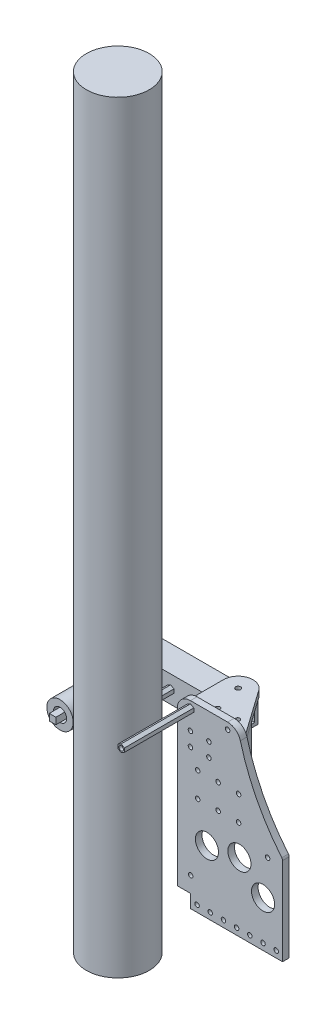
SolidWorks part; units mm, degrees
ref_plane "Front Plane" through (0, 0, 0) normal (0, 0, 1) x (1, 0, 0)
ref_plane "Top Plane" through (0, 0, 0) normal (0, 1, 0) x (1, 0, 0)
ref_plane "Right Plane" through (0, 0, 0) normal (1, 0, 0) x (0, 0, -1)
sketch "Elevation Bar" plane through (0, 0, 0) normal (0, 1, 0) x (1, 0, 0)
  circle A0 centre (0, 0) radius 30.226
  dimension "D1" = 60.452
extrude "Elevation Bar Part" add sketch "Elevation Bar" along normal blind 734.06
sketch "Pole and Drivetrain Pos" plane through (0, 0, 0) normal (0, 0, 1) x (1, 0, 0)
  line L0 (0, 0) -> (172.1794, 0) construction
  line L1 (-30.226, 0) -> (-30.226, 734.06) construction
  line L2 (-30.226, 734.06) -> (30.226, 734.06) construction
  line L3 (30.226, 734.06) -> (30.226, 0) construction
  line L4 (30.226, 0) -> (30.226, 734.06) construction
  line L5 (636.651, 41.275) -> (27.051, 41.275) construction
  line L6 (636.651, 53.975) -> (27.051, 53.975)
  line L7 (636.651, 53.975) -> (636.651, 28.575)
  line L8 (636.651, 28.575) -> (27.051, 28.575)
  line L9 (27.051, 53.975) -> (27.051, 28.575)
  line L10 (-30.226, 93.98) -> (30.226, 93.98) construction
  line L11 (33.2486, 0) -> (-33.2486, 0) construction
  line L12 (30.226, 185.42) -> (-30.226, 185.42) construction
  line L13 (30.226, 276.86) -> (-30.226, 276.86) construction
  line L14 (30.226, 368.3) -> (-30.226, 368.3) construction
  line L15 (30.226, 459.74) -> (-30.226, 459.74) construction
  line L16 (30.226, 551.18) -> (-30.226, 551.18) construction
  line L17 (30.226, 642.62) -> (-30.226, 642.62) construction
  line L18 (30.226, 73.152) -> (750.8896, 73.152) construction
  circle A0 centre (579.501, 41.275) radius 41.275 construction
  circle A1 centre (84.201, 41.275) radius 41.275 construction
  circle A2 centre (331.851, 41.275) radius 41.275 construction
  circle A3 centre (84.201, 41.275) radius 25.4
  point P24 (331.851, 41.275)
  dimension "D2" = 82.55
  dimension "D5" = 50.8
  dimension "D1" = 609.6
  dimension "D3" = 25.4
  dimension "D6" = 93.98
  dimension "D7" = 185.42
  dimension "D8" = 276.86
  dimension "D9" = 368.3
  dimension "D10" = 459.74
  dimension "D11" = 551.18
  dimension "D12" = 642.62
  dimension "D13" = 73.152
  dimension "D14" = 57.15
  dimension "D4" = 57.15
  dimension "D15" = 6.35
sketch "Driving Wheels Geo" plane through (0, 0, 0) normal (0, 0, 1) x (1, 0, 0)
  line L0 (-30.226, 182.88) -> (-30.226, 101.727) construction
  line L1 (55.626, 101.727) -> (30.226, 101.727) construction
  line L2 (-30.226, 0) -> (-30.226, 734.06) construction
  line L3 (30.226, 734.06) -> (30.226, 0) construction
  line L5 (30.226, 101.727) -> (-30.226, 101.727) construction
  line L6 (-30.226, 182.88) -> (30.226, 101.727) construction
  line L7 (31.8135, 101.727) -> (-30.226, 182.88) construction
  line L8 (30.226, 227.417) -> (203.668, 53.975) construction
  line L9 (-42.926, 195.58) -> (44.8729, 195.58) construction
  line L10 (30.226, 73.152) -> (750.8896, 73.152) construction
  line L11 (636.651, 53.975) -> (27.051, 53.975) construction
  line L14 (-42.926, 170.18) -> (44.8729, 170.18) construction
  line L15 (44.8729, 170.18) -> (44.8729, 195.58) construction
  line L16 (81.026, 28.575) -> (81.026, 257.175) construction
  line L17 (32.1729, 195.58) -> (57.5729, 195.58) construction
  line L18 (32.1729, 195.58) -> (32.1729, 170.18) construction
  line L19 (32.1729, 170.18) -> (57.5729, 170.18) construction
  line L20 (57.5729, 195.58) -> (57.5729, 170.18) construction
  line L21 (32.1729, 195.58) -> (57.5729, 170.18) construction
  line L22 (32.1729, 170.18) -> (57.5729, 195.58) construction
  line L23 (636.651, 28.575) -> (27.051, 28.575) construction
  line L24 (284.226, 257.175) -> (81.026, 257.175) construction
  line L25 (284.226, 257.175) -> (284.226, 53.975) construction
  line L26 (81.026, 257.175) -> (30.226, 257.175) construction
  circle A1 centre (55.626, 101.727) radius 25.4
  circle A3 centre (-42.926, 182.88) radius 12.7
  circle A4 centre (81.026, 104.775) radius 50.8 construction
  circle A5 centre (55.626, 101.727) radius 23.8125 construction
  circle A7 centre (284.226, 257.175) radius 203.2 construction
  point P28 (44.8729, 182.88)
  dimension "D1" = 50.8
  dimension "D2" = 1.5875
  dimension "D3" = 52.603
  dimension "D4" = 3.175
  dimension "D5" = 182.88
  dimension "D8" = 101.6
  dimension "D6" = 25.4
  dimension "D13" = 3.175
  dimension "D14" = 50.8
  dimension "D16" = 406.4
  dimension "D7" = 81.153
  dimension "D9" = 45
  dimension "D10" = 53.317
  dimension "D11" = 25.4
  dimension "D12" = 47.752
ref_plane "Plane1" through (0, 182.88, 0) normal (0, 1, 0) x (1, 0, 0)
sketch "Clamp Geo" plane through (0, 182.88, 0) normal (0, 1, 0) x (1, 0, 0)
  line L0 (-42.926, -19.8438) -> (-42.926, 87.3125) construction
  line L3 (27.051, 228.6) -> (27.051, -228.6) construction
  line L4 (47.6, 61.9125) -> (-49.276, 61.9125)
  line L5 (47.6, 61.9125) -> (47.6, 87.3125)
  line L6 (47.6, 87.3125) -> (-49.276, 87.3125)
  line L7 (-49.276, 61.9125) -> (-49.276, 87.3125)
  line L10 (-46.101, 87.3125) -> (-39.751, 87.3125)
  line L11 (-46.101, 87.3125) -> (-46.101, -19.8438)
  line L12 (-46.101, -19.8438) -> (-39.751, -19.8438)
  line L13 (-39.751, 87.3125) -> (-39.751, -19.8438)
  line L14 (-55.626, 12.7) -> (-30.226, 12.7) construction
  line L15 (-55.626, 12.7) -> (-55.626, -12.7) construction
  line L16 (-55.626, -12.7) -> (-30.226, -12.7) construction
  line L17 (-30.226, 12.7) -> (-30.226, -12.7) construction
  line L18 (-55.626, 12.7) -> (-30.226, -12.7) construction
  line L19 (-55.626, -12.7) -> (-30.226, 12.7) construction
  line L20 (0, -30.226) -> (0, 30.226) construction
  line L21 (-30.226, 0) -> (30.226, 0) construction
  line L22 (-46.101, 80.9625) -> (-42.926, 80.9625) construction
  line L23 (-39.751, 74.6125) -> (-46.101, 74.6125)
  line L24 (-46.101, 74.6125) -> (-46.101, 87.3125) construction
  line L25 (-39.751, 61.9125) -> (-39.751, 87.3125) construction
  line L26 (47.6, 74.6125) -> (41.25, 74.6125) construction
  line L27 (-11.049, 36.5125) -> (-11.049, 61.9125) construction
  line L28 (-14.224, 61.9125) -> (-7.874, 61.9125)
  line L29 (-14.224, 61.9125) -> (-14.224, 36.5125)
  line L30 (-14.224, 36.5125) -> (-7.874, 36.5125)
  line L31 (-7.874, 61.9125) -> (-7.874, 36.5125)
  circle A0 centre (0, 0) radius 30.226 construction
  circle A3 centre (-42.926, 80.9625) radius 1.8288
  circle A5 centre (-42.926, 68.2625) radius 1.8288
  circle A6 centre (41.25, 74.6125) radius 3.175
  circle A7 centre (41.25, 74.6125) radius 14.199 construction
  point P14 (-42.926, 0)
  point P32 (-39.751, 74.6125)
  point P34 (-46.101, 74.6125)
  point P36 (-42.926, 74.6125)
  point P42 (47.6, 74.6125)
  dimension "D1" = 60.452
  dimension "D4" = 61.9125
  dimension "D7" = 3.6576
  dimension "D8" = 3.175
  dimension "D10" = 6.35
  dimension "D11" = 3.175
  dimension "D12" = 25.4
  dimension "D2" = 457.2
  dimension "D3" = 25.4
  dimension "D5" = 6.35
  dimension "D6" = 25.4
  dimension "D9" = 96.876
  dimension "D13" = 7.1437
  dimension "D14" = 6.35
  dimension "D15" = 38.1
extrude "Boss-Extrude1" add sketch "Clamp Geo" along normal blind 12.7 and the other way blind 12.7 separate body contours L6 L13 L4 L5 A6 | L11 L6 L7 L4 | L13 L23 L11 L4 A5 | L23 L13 L6 L11 A3 region at (3.384, 182.88, -74.6125) region at (-39.893, 182.88, -80.9625) region at (-42.926, 182.88, -62.0545) region at (-47.6885, 182.88, -74.6125)
sketch "Locked Setting Geo" plane through (0, 182.88, 0) normal (0, 1, 0) x (1, 0, 0)
  line L0 (30.9086, 201.0486) -> (105.8246, 124.4323) construction
  line L1 (27.7805, 74.7636) -> (97.0464, 142.4925)
  line L2 (27.7805, 74.7636) -> (41.0989, 61.143)
  line L3 (41.0989, 61.143) -> (110.3649, 128.8718)
  line L4 (97.0464, 142.4925) -> (110.3649, 128.8718)
  line L5 (108.0947, 126.6521) -> (103.5545, 122.2126)
  line L6 (108.0947, 126.6521) -> (33.1787, 203.2683)
  line L7 (33.1787, 203.2683) -> (28.6385, 198.8288)
  line L8 (103.5545, 122.2126) -> (28.6385, 198.8288)
  line L9 (64.9611, 184.3888) -> (46.8002, 166.6309) construction
  line L10 (64.9611, 184.3888) -> (47.2032, 202.5497) construction
  line L11 (47.2032, 202.5497) -> (29.0423, 184.7918) construction
  line L12 (46.8002, 166.6309) -> (29.0423, 184.7918) construction
  line L13 (64.9611, 184.3888) -> (29.0423, 184.7918) construction
  line L14 (47.2032, 202.5497) -> (46.8002, 166.6309) construction
  line L15 (-7.874, 61.9125) -> (-7.874, 36.5125) construction
  line L16 (69.7143, 115.7669) -> (51.9564, 133.9278)
  line L17 (104.7651, 130.0572) -> (102.495, 127.8375) construction
  line L18 (96.8953, 129.0229) -> (101.4355, 133.4624)
  line L19 (101.4355, 133.4624) -> (108.0947, 126.6521) construction
  line L20 (90.2361, 135.8333) -> (103.5545, 122.2126) construction
  line L21 (34.4397, 67.9533) -> (41.25, 74.6125) construction
  line L22 (47.6, 87.3125) -> (-49.276, 87.3125) construction
  line L23 (-46.101, 87.3125) -> (-46.101, -19.8438) construction
  line L24 (27.051, 228.6) -> (27.051, -228.6) construction
  line L25 (51.9564, 133.9278) -> (56.4967, 138.3672)
  line L26 (56.4967, 138.3672) -> (74.2545, 120.2063)
  circle A1 centre (102.495, 127.8375) radius 1.8288
  circle A2 centre (95.8358, 134.6478) radius 1.8288
  circle A3 centre (41.25, 74.6125) radius 6.35
  point P0 (-42.926, 74.6125)
  point P9 (-42.926, 0)
  point P10 (47.0017, 184.5903)
  point P28 (96.8953, 129.0229)
  point P30 (101.4355, 133.4624)
  point P32 (99.1654, 131.2427)
  point P36 (34.4397, 67.9533)
  point P40 (41.25, 74.6125)
  dimension "D7" = 3.175
  dimension "D6" = 3.6576
  dimension "D9" = 12.7
  dimension "D2" = 19.05
  dimension "D4" = 6.35
  dimension "D5" = 25.4
  dimension "D8" = 96.876
  dimension "D10" = 3.175
  dimension "D3" = 1.5875
  dimension "D12" = 83.3139
  dimension "D11" = 74.6125
  dimension "D13" = 74.6125
  dimension "D14" = 49.124
  dimension "D15" = 6.35
  dimension "D16" = 25.4
  dimension "D17" = 49.124
sketch "Sketch2" plane through (-49.276, 0, 0) normal (-1, 0, 0) x (0, 0, 1)
  line L0 (-74.6125, 195.58) -> (-74.6125, 170.18) construction
  line L1 (-61.9125, 195.58) -> (-87.3125, 195.58) construction
  line L2 (-61.9125, 170.18) -> (-87.3125, 170.18) construction
  line L3 (-61.9125, 170.18) -> (-61.9125, 195.58) construction
  line L4 (-84.1375, 173.355) -> (-65.0875, 173.355)
  line L5 (-84.1375, 173.355) -> (-84.1375, 192.405)
  line L6 (-84.1375, 192.405) -> (-65.0875, 192.405)
  line L7 (-65.0875, 173.355) -> (-65.0875, 192.405)
  line L8 (-84.1375, 173.355) -> (-65.0875, 192.405) construction
  line L9 (-84.1375, 192.405) -> (-65.0875, 173.355) construction
  point P6 (-74.6125, 182.88)
  dimension "D1" = 3.175
  dimension "D2" = 3.175
extrude "Cut-Extrude2" cut sketch "Sketch2" against normal up to surface (96.876 mm away) up to face at (47.6, 182.88, -74.6125)
sketch "Sketch3" plane through (0, 0, -87.3125) normal (0, 0, -1) x (-1, 0, 0)
  line L2 (39.7129, 179.6669) -> (46.1391, 179.6669) construction
  line L3 (39.7129, 179.6669) -> (39.7129, 186.0931) construction
  line L4 (39.7129, 186.0931) -> (46.1391, 186.0931) construction
  line L5 (46.1391, 179.6669) -> (46.1391, 186.0931) construction
  line L6 (39.7129, 179.6669) -> (46.1391, 186.0931) construction
  line L7 (39.7129, 186.0931) -> (46.1391, 179.6669) construction
  circle A1 centre (42.926, 182.88) radius 4.544
  point P0 (42.926, 182.88)
  point P1 (42.926, 182.88)
  dimension "D1" = 6.4262
extrude "Cut-Extrude3" cut sketch "Sketch3" against normal up to surface (25.4 mm away) up to face at (-0.838, 182.88, -61.9125)
extrude "Boss-Extrude2" add sketch "Clamp Geo<3>" along normal blind 3.175 and the other way blind 3.175 separate body contours L13 L4 L11 L12 | L13 L23 L11 L4 A5 | L23 L13 L6 L11 A3 region at (-39.893, 182.88, -80.9625) region at (-42.926, 182.88, -21.0344) region at (-42.926, 182.88, -62.0545)
sketch "Clamp Geo<3>" plane through (0, 182.88, 0) normal (0, 1, 0) x (1, 0, 0) same geometry as "Clamp Geo"
sketch "Custom Driven Flywheel" plane through (0, 0, 0) normal (0, 0, 1) x (1, 0, 0)
  circle A0 centre (-42.926, 182.88) radius 12.7 construction
  circle A1 centre (-42.926, 182.88) radius 12.7
  circle A2 centre (-42.926, 182.88) radius 6.35
  dimension "D1" = 12.7
extrude "Boss-Extrude3" add sketch "Custom Driven Flywheel" along normal blind 12.7 and the other way blind 25.4 separate body
sketch "Sketch8" plane through (0, 173.355, 0) normal (0, 1, 0) x (1, 0, 0)
  line L0 (-42.926, 84.1375) -> (-42.926, 65.0875) construction
  line L5 (-36.576, 74.6125) -> (-42.926, 74.6125) construction
  line L6 (-42.926, 74.6125) -> (-49.276, 74.6125) construction
  line L11 (47.6, 65.0875) -> (-49.276, 65.0875) construction
  line L12 (47.6, 84.1375) -> (-49.276, 84.1375) construction
  line L13 (47.6, 65.0875) -> (-49.276, 65.0875) construction
  line L14 (47.6, 84.1375) -> (-49.276, 84.1375) construction
  line L15 (-49.276, 84.1375) -> (-49.276, 65.0875) construction
  line L17 (-49.276, 65.3415) -> (-36.576, 65.3415)
  line L18 (-49.276, 65.3415) -> (-49.276, 83.8835)
  line L19 (-49.276, 83.8835) -> (-36.576, 83.8835)
  line L20 (-36.576, 65.3415) -> (-36.576, 83.8835)
  line L21 (-49.276, 65.3415) -> (-36.576, 83.8835) construction
  line L22 (-49.276, 83.8835) -> (-36.576, 65.3415) construction
  circle A0 centre (-42.926, 80.9625) radius 1.8288 construction
  circle A1 centre (-42.926, 80.9625) radius 1.8288 construction
  circle A2 centre (-42.926, 68.2625) radius 1.8288 construction
  circle A3 centre (-42.926, 80.9625) radius 1.8288
  circle A4 centre (-42.926, 68.2625) radius 1.8288
  dimension "D1" = 0.254
extrude "Boss-Extrude5" add sketch "Sketch8" along normal up to surface (9.525 mm away) separate body up to plane "Plane1"
sketch "Sketch10" plane through (0, 182.88, 0) normal (0, 1, 0) x (1, 0, 0)
  line L0 (-36.576, 83.8835) -> (-49.276, 83.8835) construction
  line L8 (-39.751, 65.3415) -> (-46.101, 65.3415)
  line L9 (-39.751, 65.3415) -> (-39.751, 83.8835)
  line L10 (-39.751, 83.8835) -> (-46.101, 83.8835)
  line L11 (-46.101, 65.3415) -> (-46.101, 83.8835)
  line L12 (-39.751, 65.3415) -> (-46.101, 83.8835) construction
  line L13 (-39.751, 83.8835) -> (-46.101, 65.3415) construction
  circle A0 centre (-42.926, 68.2625) radius 1.8288 construction
  circle A1 centre (-42.926, 80.9625) radius 1.8288 construction
  circle A2 centre (-42.926, 68.2625) radius 1.8288
  circle A3 centre (-42.926, 80.9625) radius 1.8288
  point P0 (-42.926, 74.6125)
  dimension "D1" = 6.35
extrude "Cut-Extrude5" cut sketch "Sketch10" against normal blind 3.175
ref_plane "Plane2" through (0, 0, 210.82) normal (0, 0, 1) x (1, 0, 0)
ref_plane "Plane3" through (0, 0, 166.37) normal (0, 0, 1) x (1, 0, 0)
sketch "Sketch12" plane through (0, 0, 166.37) normal (0, 0, 1) x (1, 0, 0)
  line L0 (636.651, 41.275) -> (27.051, 41.275) construction
  line L1 (636.651, 41.275) -> (27.051, 41.275) construction
  line L2 (84.201, 41.275) -> (96.901, 41.275) construction
  line L3 (109.601, 41.275) -> (109.601, 85.2691) construction
  circle A0 centre (84.201, 41.275) radius 25.4 construction
  circle A1 centre (84.201, 41.275) radius 25.4
  circle A2 centre (55.626, 101.727) radius 21.1667
  circle A4 centre (86.8604, 107.4259) radius 10.5833
  circle A5 centre (128.651, 41.275) radius 19.05
  circle A7 centre (86.8604, 107.4259) radius 21.1667
  circle A8 centre (109.601, 85.2691) radius 10.5833
  circle A9 centre (109.601, 85.2691) radius 25.4
  circle A10 centre (84.201, 41.275) radius 3.175 construction
  circle A11 centre (96.901, 41.275) radius 3.175 construction
  circle A12 centre (109.601, 41.275) radius 3.175 construction
  circle A13 centre (122.301, 41.275) radius 3.175 construction
  circle A14 centre (135.001, 41.275) radius 3.175 construction
  circle A15 centre (147.701, 41.275) radius 3.175 construction
  circle A16 centre (160.401, 41.275) radius 3.175 construction
  circle A17 centre (173.101, 41.275) radius 3.175 construction
  circle A18 centre (185.801, 41.275) radius 3.175 construction
  circle A19 centre (198.501, 41.275) radius 3.175 construction
  point P3 (55.626, 101.727)
  dimension "D1" = 42.3333
  dimension "D2" = 21.1667
  dimension "D3" = 50.8
  dimension "D4" = 38.1
  dimension "D5" = 42.3333
  dimension "D6" = 21.1667
  dimension "D8" = 6.35
  dimension "D10" = 12.7
  dimension "D9" = 10
sketch "Sketch13" plane through (0, 0, 210.82) normal (0, 0, 1) x (1, 0, 0)
  line L0 (109.601, 72.5691) -> (109.601, 97.9691) construction
  line L2 (90.551, 72.5691) -> (90.551, 97.9691)
  line L4 (154.051, 72.5691) -> (154.051, 97.9691)
  line L5 (147.701, 85.2691) -> (147.701, 41.275) construction
  line L6 (109.601, 85.2691) -> (154.051, 85.2691) construction
  line L7 (90.551, 85.2691) -> (109.601, 85.2691) construction
  line L8 (90.551, 97.9691) -> (109.601, 97.9691)
  line L9 (90.551, 72.5691) -> (109.601, 72.5691)
  line L10 (109.601, 97.9691) -> (154.051, 97.9691)
  line L11 (154.051, 72.5691) -> (109.601, 72.5691)
  circle A0 centre (109.601, 85.2691) radius 3.175 construction
  circle A1 centre (96.901, 85.2691) radius 3.175 construction
  circle A2 centre (147.701, 85.2691) radius 3.175 construction
  point P0 (109.601, 85.2691)
  dimension "D2" = 6.35
  dimension "D3" = 6.35
  dimension "D6" = 6.35
  dimension "D1" = 25.4
  dimension "D4" = 12.7
  dimension "D5" = 6.35
ref_plane "Plane5" through (0, 0, 146.177) normal (0, 0, 1) x (1, 0, 0)
sketch "Sketch15" plane through (0, 0, 146.177) normal (0, 0, 1) x (1, 0, 0)
  line L0 (90.551, 72.5691) -> (109.601, 72.5691) construction
  line L1 (154.051, 72.5691) -> (109.601, 72.5691) construction
  line L2 (154.051, 72.5691) -> (154.051, 97.9691) construction
  line L3 (109.601, 97.9691) -> (154.051, 97.9691) construction
  line L4 (90.551, 97.9691) -> (109.601, 97.9691) construction
  line L5 (90.551, 72.5691) -> (90.551, 97.9691) construction
  line L6 (90.551, 72.5691) -> (109.601, 72.5691)
  line L7 (154.051, 72.5691) -> (109.601, 72.5691)
  line L8 (154.051, 72.5691) -> (154.051, 97.9691)
  line L9 (109.601, 97.9691) -> (154.051, 97.9691)
  line L10 (90.551, 97.9691) -> (109.601, 97.9691)
  line L11 (90.551, 72.5691) -> (90.551, 97.9691)
  line L12 (90.551, 28.575) -> (109.601, 28.575)
  line L13 (154.051, 28.575) -> (109.601, 28.575)
  line L14 (154.051, 28.575) -> (154.051, 53.975)
  line L15 (109.601, 53.975) -> (154.051, 53.975)
  line L16 (90.551, 53.975) -> (109.601, 53.975)
  line L17 (90.551, 28.575) -> (90.551, 53.975)
  line L18 (154.051, 28.575) -> (90.551, 53.975) construction
  line L19 (109.601, 53.975) -> (109.601, 28.575) construction
  line L20 (154.051, 41.275) -> (90.551, 41.275) construction
  circle A0 centre (109.601, 85.2691) radius 3.175 construction
  circle A1 centre (109.601, 85.2691) radius 3.175
  circle A2 centre (109.601, 41.275) radius 3.175 construction
  dimension "D5" = 6.35
  dimension "D1" = 68.3916
  dimension "D2" = 68.3916
  dimension "D3" = 19.05
  dimension "D4" = 25.4
ref_plane "Plane6" through (0, 53.975, 0) normal (0, 1, 0) x (1, 0, 0)
sketch "Sketch16" plane through (0, 53.975, 0) normal (0, 1, 0) x (1, 0, 0)
  line L0 (27.051, -127) -> (27.051, 127)
  line L1 (33.401, 120.65) -> (33.401, 107.95) construction
  line L2 (27.051, 127) -> (39.751, 127)
  line L3 (27.051, 127) -> (27.051, -127)
  line L4 (27.051, -127) -> (39.751, -127)
  line L5 (39.751, 127) -> (39.751, -127)
  line L6 (33.401, 120.65) -> (33.401, 127) construction
  line L7 (135.001, -166.37) -> (135.001, -127) construction
  line L8 (636.651, 0) -> (27.051, 0) construction
  line L9 (128.651, 127) -> (141.351, 127)
  line L14 (128.651, 127) -> (128.651, -127)
  line L15 (128.651, -127) -> (141.351, -127)
  line L16 (141.351, 127) -> (141.351, -127)
  line L17 (128.651, 127) -> (141.351, -127) construction
  line L18 (128.651, -127) -> (141.351, 127) construction
  line L19 (135.001, -120.65) -> (135.001, -107.95) construction
  line L20 (135.001, -127) -> (135.001, -120.65) construction
  circle A0 centre (33.401, 120.65) radius 3.175
  circle A1 centre (33.401, 107.95) radius 3.175
  circle A2 centre (33.401, 95.25) radius 3.175
  circle A3 centre (33.401, 82.55) radius 3.175
  circle A4 centre (33.401, 69.85) radius 3.175
  circle A5 centre (33.401, 57.15) radius 3.175
  circle A6 centre (33.401, 44.45) radius 3.175
  circle A7 centre (33.401, 31.75) radius 3.175
  circle A8 centre (33.401, 19.05) radius 3.175
  circle A9 centre (33.401, 6.35) radius 3.175
  circle A10 centre (33.401, -6.35) radius 3.175
  circle A11 centre (33.401, -19.05) radius 3.175
  circle A12 centre (33.401, -31.75) radius 3.175
  circle A13 centre (33.401, -44.45) radius 3.175
  circle A14 centre (33.401, -57.15) radius 3.175
  circle A15 centre (33.401, -69.85) radius 3.175
  circle A16 centre (33.401, -82.55) radius 3.175
  circle A17 centre (33.401, -95.25) radius 3.175
  circle A18 centre (33.401, -107.95) radius 3.175
  circle A19 centre (33.401, -120.65) radius 3.175
  circle A40 centre (135.001, -120.65) radius 3.175
  circle A41 centre (135.001, -107.95) radius 3.175
  circle A42 centre (135.001, -95.25) radius 3.175
  circle A43 centre (135.001, -82.55) radius 3.175
  circle A44 centre (135.001, -69.85) radius 3.175
  circle A45 centre (135.001, -57.15) radius 3.175
  circle A46 centre (135.001, -44.45) radius 3.175
  circle A47 centre (135.001, -31.75) radius 3.175
  circle A48 centre (135.001, -19.05) radius 3.175
  circle A49 centre (135.001, -6.35) radius 3.175
  circle A50 centre (135.001, 6.35) radius 3.175
  circle A51 centre (135.001, 19.05) radius 3.175
  circle A52 centre (135.001, 31.75) radius 3.175
  circle A53 centre (135.001, 44.45) radius 3.175
  circle A54 centre (135.001, 57.15) radius 3.175
  circle A55 centre (135.001, 69.85) radius 3.175
  circle A56 centre (135.001, 82.55) radius 3.175
  circle A57 centre (135.001, 95.25) radius 3.175
  circle A58 centre (135.001, 107.95) radius 3.175
  circle A59 centre (135.001, 120.65) radius 3.175
  point P3 (27.051, 0)
  point P9 (135.001, -166.37)
  point P51 (135.001, 0)
  dimension "D3" = 6.35
  dimension "D1" = 254
  dimension "D2" = 12.7
  dimension "D4" = 6.35
  dimension "D6" = 12.7
  dimension "D10" = 6.35
  dimension "D12" = 12.7
  dimension "D5" = 20
  dimension "D11" = 20
sketch "Sketch18" plane through (0, 53.975, 0) normal (0, 1, 0) x (1, 0, 0)
  line L0 (39.751, -36.5125) -> (128.651, -36.5125)
  line L1 (39.751, 127) -> (39.751, -127) construction
  line L2 (128.651, 127) -> (128.651, -127) construction
  line L3 (636.651, 0) -> (27.051, 0) construction
  line L4 (39.751, -49.2125) -> (128.651, -49.2125)
  line L5 (39.751, -36.5125) -> (39.751, -49.2125)
  line L6 (128.651, -36.5125) -> (128.651, -49.2125)
  line L7 (39.751, -42.8625) -> (128.651, -42.8625) construction
  line L8 (46.101, -42.8625) -> (58.801, -42.8625) construction
  line L9 (-403.733, 0) -> (403.733, 0) construction
  line L10 (46.101, 42.8625) -> (58.801, 42.8625) construction
  line L11 (39.751, 42.8625) -> (128.651, 42.8625) construction
  line L12 (128.651, 36.5125) -> (128.651, 49.2125)
  line L13 (39.751, 36.5125) -> (39.751, 49.2125)
  line L14 (39.751, 49.2125) -> (128.651, 49.2125)
  line L15 (39.751, 36.5125) -> (128.651, 36.5125)
  circle A0 centre (46.101, -42.8625) radius 3.175
  circle A1 centre (58.801, -42.8625) radius 3.175
  circle A2 centre (71.501, -42.8625) radius 3.175
  circle A3 centre (84.201, -42.8625) radius 3.175
  circle A4 centre (96.901, -42.8625) radius 3.175
  circle A5 centre (109.601, -42.8625) radius 3.175
  circle A6 centre (122.301, -42.8625) radius 3.175
  circle A7 centre (122.301, 42.8625) radius 3.175
  circle A8 centre (109.601, 42.8625) radius 3.175
  circle A9 centre (96.901, 42.8625) radius 3.175
  circle A10 centre (84.201, 42.8625) radius 3.175
  circle A11 centre (71.501, 42.8625) radius 3.175
  circle A12 centre (58.801, 42.8625) radius 3.175
  circle A13 centre (46.101, 42.8625) radius 3.175
  point P50 (0, 0)
  dimension "D4" = 6.35
  dimension "D1" = 36.5125
  dimension "D2" = 12.7
  dimension "D3" = 6.35
  dimension "D6" = 12.7
  dimension "D5" = 7
ref_plane "Plane7" through (0, 0, -36.5125) normal (0, 0, 1) x (1, 0, 0)
sketch "Sketch17" plane through (0, 0, -36.5125) normal (0, 0, 1) x (1, 0, 0)
  line L2 (128.397, 125.6137) -> (128.397, 53.975)
  line L6 (128.651, 53.975) -> (141.351, 53.975) construction
  line L9 (636.651, 53.975) -> (27.051, 53.975) construction
  line L10 (40.005, 53.975) -> (40.005, 41.275)
  line L11 (40.005, 41.275) -> (128.397, 41.275)
  line L13 (128.397, 53.975) -> (128.397, 41.275)
  line L14 (55.626, 101.727) -> (55.626, 41.275) construction
  line L17 (27.051, 53.975) -> (27.051, 201.93)
  line L20 (40.005, 53.975) -> (27.051, 53.975)
  line L21 (-42.926, 170.18) -> (44.8729, 170.18) construction
  line L23 (39.751, 214.63) -> (39.751, 208.28) construction
  line L24 (39.751, 208.28) -> (75.5138, 208.28) construction
  line L25 (75.5138, 214.63) -> (75.5138, 208.28) construction
  line L26 (27.051, 160.02) -> (105.7571, 160.02) construction
  line L27 (27.051, 160.02) -> (27.051, 136.2126) construction
  line L28 (27.051, 136.2126) -> (105.7571, 136.2126) construction
  line L29 (105.7571, 160.02) -> (105.7571, 136.2126) construction
  line L30 (66.4041, 160.02) -> (66.4041, 136.2126) construction
  line L31 (46.7275, 160.02) -> (46.7275, 136.2126) construction
  line L32 (66.4041, 148.1163) -> (27.051, 148.1163) construction
  line L33 (86.8604, 107.4259) -> (127.6682, 127.6377) construction
  line L34 (40.005, 53.975) -> (40.005, 69.215) construction
  line L35 (39.751, 214.63) -> (75.5138, 214.63)
  line L36 (57.6324, 208.28) -> (57.6324, 214.63) construction
  line L37 (47.6, 195.58) -> (-49.276, 195.58) construction
  circle A0 centre (55.626, 101.727) radius 11.1125
  circle A1 centre (86.8604, 107.4259) radius 11.1125
  circle A2 centre (109.601, 85.2691) radius 11.1125
  circle A6 centre (284.226, 257.175) radius 203.2 construction
  arc A7 (87.7909, 205.1797) -> (127.6682, 127.6377) centre (284.226, 257.175) ccw
  arc A9 (128.397, 125.6137) -> (127.6682, 127.6377) centre (125.222, 125.6137) ccw
  arc A10 (87.7909, 205.1797) -> (75.5138, 214.63) centre (75.5138, 201.93) ccw
  arc A11 (27.051, 201.93) -> (39.751, 214.63) centre (39.751, 201.93) cw
  circle A12 centre (39.751, 208.28) radius 2.1527
  circle A13 centre (75.5138, 208.28) radius 2.1527
  circle A14 centre (86.8604, 107.4259) radius 21.1667 construction
  circle A15 centre (46.7275, 160.02) radius 2.1527
  circle A16 centre (66.4041, 160.02) radius 2.1527
  circle A17 centre (66.4041, 136.2126) radius 2.1527
  circle A18 centre (46.7275, 136.2126) radius 2.1527
  circle A19 centre (86.0806, 136.2126) radius 2.1527
  circle A20 centre (86.0806, 160.02) radius 2.1526
  circle A21 centre (114.0115, 120.8737) radius 2.1527
  circle A22 centre (40.005, 69.215) radius 2.1527
  point P14 (0, 0)
  point P25 (128.397, 126.762)
  point P54 (46.7275, 148.1163)
  point P69 (0, 0)
  point P70 (0, 0)
  dimension "D1" = 22.225
  dimension "D7" = 3.175
  dimension "D6" = 12.7
  dimension "D9" = 4.3053
  dimension "D12" = 4.3053
  dimension "D4" = 12.7
  dimension "D5" = 12.954
  dimension "D3" = 12.954
  dimension "D8" = 6.35
  dimension "D10" = 10.16
  dimension "D11" = 7.62
  dimension "D13" = 15.24
  dimension "D14" = 15.24
  dimension "D2" = 19.05
extrude "Boss-Extrude6" add sketch "Sketch17" along normal blind 6.35 separate body
sketch "Sketch19" plane through (0, 0, 0) normal (0, 0, 1) x (1, 0, 0)
  line L0 (46.101, 47.625) -> (122.301, 47.625) construction
  line L1 (46.101, 41.275) -> (46.101, 53.975) construction
  line L2 (636.651, 41.275) -> (27.051, 41.275) construction
  line L3 (636.651, 53.975) -> (27.051, 53.975) construction
  line L4 (46.101, 47.625) -> (58.801, 47.625) construction
  circle A0 centre (46.101, 47.625) radius 2.1527
  circle A1 centre (58.801, 47.625) radius 2.1527
  circle A2 centre (71.501, 47.625) radius 2.1527
  circle A3 centre (84.201, 47.625) radius 2.1527
  circle A4 centre (96.901, 47.625) radius 2.1527
  circle A5 centre (109.601, 47.625) radius 2.1527
  circle A6 centre (122.301, 47.625) radius 2.1527
  dimension "D2" = 4.3053
  dimension "D1" = 6.35
  dimension "D4" = 12.7
  dimension "D3" = 7
sketch "Sketch22" plane through (0, 53.975, 0) normal (0, 1, 0) x (1, 0, 0)
  line L0 (-52.7651, -82.55) -> (244.2686, -82.55) construction
  line L1 (-298.6786, 0) -> (298.6786, 0) construction
  line L2 (-52.7651, 82.55) -> (244.2686, 82.55) construction
  line L4 (39.751, 49.2125) -> (128.651, 49.2125) construction
  dimension "D1" = 165.1
extrude "Cut-Extrude6" cut sketch "Sketch19" against normal up to surface (36.5125 mm away) up to face at (116.1642, 120.8737, -36.5125)
ref_plane "Plane8" through (0, 197.1675, 0) normal (0, 1, 0) x (1, 0, 0)
sketch "Sketch23" plane through (0, 197.1675, 0) normal (0, 1, 0) x (1, 0, 0)
  line L0 (27.051, 74.6125) -> (27.051, 36.5125)
  line L1 (48.2536, 36.5125) -> (43.9483, 36.5125) construction
  line L2 (27.051, 36.5125) -> (85.471, 36.5125)
  line L3 (85.471, 36.5125) -> (52.8565, 82.7919)
  line L4 (27.051, 59.9055) -> (68.9853, 59.9055) construction
  line L5 (48.0181, 59.9055) -> (48.0181, 36.5125) construction
  line L6 (87.7909, 36.5125) -> (127.6682, 36.5125) construction
  line L7 (48.0181, 48.209) -> (27.051, 48.209) construction
  line L9 (48.0181, 48.209) -> (67.0681, 48.209) construction
  circle A0 centre (41.25, 74.6125) radius 14.199 construction
  circle A1 centre (41.25, 74.6125) radius 14.199
  circle A4 centre (48.0181, 48.209) radius 2.1527
  circle A7 centre (41.25, 74.6125) radius 2.3812
  circle A8 centre (67.0681, 48.209) radius 2.1527
  dimension "D4" = 4.3053
  dimension "D3" = 4.7625
  dimension "D2" = 0.508
  dimension "D1" = 58.42
  dimension "D5" = 19.05
extrude "Boss-Extrude7" add sketch "Sketch23" along normal blind 6.35 separate body contours A1 L0 L2 L3 A4 | A1 L0 | A1 | A1 | A1 | A1 region at (52.1618, 197.1675, -50.5072) region at (37.0811, 197.1675, -87.765)
sketch "Sketch25" plane through (0, 197.1675, 0) normal (0, -1, 0) x (1, 0, 0)
  line L0 (85.471, -36.5125) -> (52.8565, -82.7919) construction
  line L1 (27.051, -36.5125) -> (85.471, -36.5125) construction
  line L2 (27.051, -74.6125) -> (27.051, -36.5125) construction
  line L3 (27.051, -59.9055) -> (68.9853, -59.9055) construction
  line L4 (85.471, -36.5125) -> (69.7441, -58.8286)
  line L5 (27.051, -36.5125) -> (85.471, -36.5125)
  line L6 (27.051, -57.3655) -> (27.051, -36.5125)
  line L7 (29.591, -59.9055) -> (67.6679, -59.9055)
  circle A0 centre (48.0181, -48.209) radius 2.1526 construction
  circle A2 centre (48.0181, -48.209) radius 2.1527
  arc A4 (67.6679, -59.9055) -> (69.7441, -58.8286) centre (67.6679, -57.3655) ccw
  arc A5 (29.591, -59.9055) -> (27.051, -57.3655) centre (29.591, -57.3655) cw
  circle A6 centre (67.0681, -48.209) radius 2.1527 construction
  circle A7 centre (67.0681, -48.209) radius 2.1527
  dimension "D1" = 2.54
extrude "Boss-Extrude8" add sketch "Sketch25" along normal blind 28.829 separate body
sketch "Sketch26" plane through (0, 0, -59.9055) normal (0, 0, -1) x (-1, 0, 0)
  line L0 (-67.6679, 197.1675) -> (-29.591, 168.3385) construction
  line L1 (-67.6679, 168.3385) -> (-29.591, 197.1675) construction
  line L3 (-57.5079, 176.0309) -> (-39.751, 176.0309) construction
  line L4 (-29.591, 197.1675) -> (-67.6679, 197.1675)
  line L5 (-67.6679, 197.1675) -> (-67.6679, 168.3385)
  line L6 (-67.6679, 168.3385) -> (-29.591, 168.3385)
  line L7 (-29.591, 168.3385) -> (-29.591, 197.1675)
  line L9 (-67.6679, 197.1675) -> (-67.6679, 168.3385) construction
  line L10 (-67.6679, 168.3385) -> (-29.591, 168.3385) construction
  line L11 (-29.591, 168.3385) -> (-29.591, 197.1675) construction
  line L12 (-57.5079, 176.0309) -> (-57.5079, 189.4751) construction
  line L13 (-57.5079, 189.4751) -> (-39.751, 189.4751) construction
  line L14 (-39.751, 176.0309) -> (-39.751, 189.4751) construction
  line L15 (-57.5079, 176.0309) -> (-39.751, 189.4751) construction
  line L16 (-57.5079, 189.4751) -> (-39.751, 176.0309) construction
  line L20 (-29.591, 197.1675) -> (-67.6679, 197.1675)
  circle A1 centre (-57.5079, 176.0309) radius 2.1527
  circle A2 centre (-39.751, 176.0309) radius 2.1527
  circle A3 centre (-57.5079, 189.4751) radius 2.1527
  circle A4 centre (-39.751, 189.4751) radius 2.1527
  point P2 (-48.6295, 182.753)
  dimension "D3" = 4.3053
  dimension "D2" = 10.16
  dimension "D1" = 0
extrude "Cut-Extrude8" cut sketch "Sketch26" against normal up to surface (29.743 mm away) contours A3 | A1 | A2 | A4 region at (57.5079, 176.0309, -59.9055) region at (39.751, 176.0309, -59.9055) region at (57.5079, 189.4751, -59.9055) region at (39.751, 189.4751, -59.9055) up to face at (43.9483, 47.625, -30.1625)
sketch "Sketch27" plane through (0, 0, -30.1625) normal (0, 0, 1) x (1, 0, 0)
  line L0 (36.576, 210.1131) -> (36.576, 206.4469)
  line L1 (39.751, 211.9462) -> (36.576, 210.1131)
  line L2 (42.926, 210.1131) -> (39.751, 211.9462)
  line L3 (42.926, 206.4469) -> (42.926, 210.1131)
  line L4 (39.751, 204.6138) -> (42.926, 206.4469)
  line L5 (36.576, 206.4469) -> (39.751, 204.6138)
  circle A0 centre (39.751, 208.28) radius 3.175 construction
  circle A1 centre (39.751, 208.28) radius 2.1526 construction
  circle A2 centre (39.751, 208.28) radius 2.1527
  point P0 (39.751, 208.28)
  point P16 (39.751, 208.28)
  point P20 (39.751, 208.28)
  dimension "D1" = 6.35
  dimension "D3" = 6
extrude "Boss-Extrude9" add sketch "Sketch27" along normal up to vertex (66.675 mm away) separate body up to point (39.751, 53.975, 36.5125)
sketch "Sketch28" plane through (0, 0, -61.9125) normal (0, 0, 1) x (1, 0, 0)
  line L0 (-11.049, 195.58) -> (-11.049, 170.18) construction
  line L1 (47.6, 195.58) -> (-49.276, 195.58) construction
  line L2 (47.6, 170.18) -> (-49.276, 170.18) construction
  line L4 (-14.224, 184.7131) -> (-14.224, 181.0469)
  line L5 (-11.049, 182.88) -> (-14.224, 182.88) construction
  line L6 (-11.049, 186.5462) -> (-14.224, 184.7131)
  line L7 (-7.874, 184.7131) -> (-11.049, 186.5462)
  line L8 (-7.874, 181.0469) -> (-7.874, 184.7131)
  line L9 (-11.049, 179.2138) -> (-7.874, 181.0469)
  line L10 (-14.224, 181.0469) -> (-11.049, 179.2138)
  circle A0 centre (-11.049, 182.88) radius 2.1527
  circle A1 centre (-11.049, 182.88) radius 3.175 construction
  point P13 (19.431, 182.88)
  point P27 (-11.049, 182.88)
  dimension "D1" = 4.3053
  dimension "D3" = 6.35
  dimension "D4" = 6
extrude "Boss-Extrude10" add sketch "Sketch28" along normal blind 25.4 separate body
sketch "Sketch31" plane through (0, 0, -61.9125) normal (0, 0, 1) x (1, 0, 0)
  circle A0 centre (-11.049, 182.88) radius 2.1527 construction
  circle A1 centre (-11.049, 182.88) radius 2.1527
extrude "Cut-Extrude9" cut sketch "Sketch31" against normal up to surface (25.4 mm away) up to face at (-47.47, 182.88, -87.3125)
sketch "Sketch32" plane through (0, 0, -36.5125) normal (0, 0, -1) x (-1, 0, 0)
  line L0 (14.224, 182.88) -> (7.874, 182.88) construction
  line L1 (14.224, 182.88) -> (7.874, 182.88) construction
  line L2 (12.5334, 188.408) -> (15.5808, 179.3836) construction
  line L3 (15.5808, 179.3836) -> (-73.7283, 149.225) construction
  line L4 (-73.7283, 149.225) -> (-42.384, 60.325) construction
  line L5 (-42.384, 60.325) -> (-33.401, 63.4922) construction
  line L6 (-73.7283, 149.225) -> (-78.6002, 163.0427) construction
  line L7 (-73.7283, 149.225) -> (-87.6097, 144.5374) construction
  line L8 (-27.051, 201.93) -> (-27.051, 53.975) construction
  line L9 (-27.051, 53.975) -> (-39.751, 53.975) construction
  circle A0 centre (11.049, 182.88) radius 3.175 construction
  point P4 (-38.8748, 80.5528)
  point P13 (-56.9588, 134.0599)
  point P14 (0, 0)
  point P15 (0, 0)
  point P16 (0, 0)
  point P18 (-19.1268, 187.3975)
  point P19 (14.0571, 183.8958)
  point P21 (-29.591, 77.2521)
  point P22 (-58.7, 114.1841)
  point P23 (-51.6022, 125.0289)
  point P24 (-49.791, 127.7962)
  point P25 (-93.2024, 160.1144)
  point P26 (-38.6191, 70.0842)
  point P29 (-78.6002, 163.0427)
  dimension "D1" = 9.525
  dimension "D2" = 6.35
  dimension "D3" = 3.175
  dimension "D4" = 6.35
equation "\"D4@Pole and Drivetrain Pos\"=\"D14@Pole and Drivetrain Pos\""
equation "\"D5@Sketch17\"=\"D3@Sketch17\""
equation "\"D11@Locked Setting Geo\"=\"D13@Locked Setting Geo\""
equation "\"D17@Locked Setting Geo\"=\"D14@Locked Setting Geo\""
